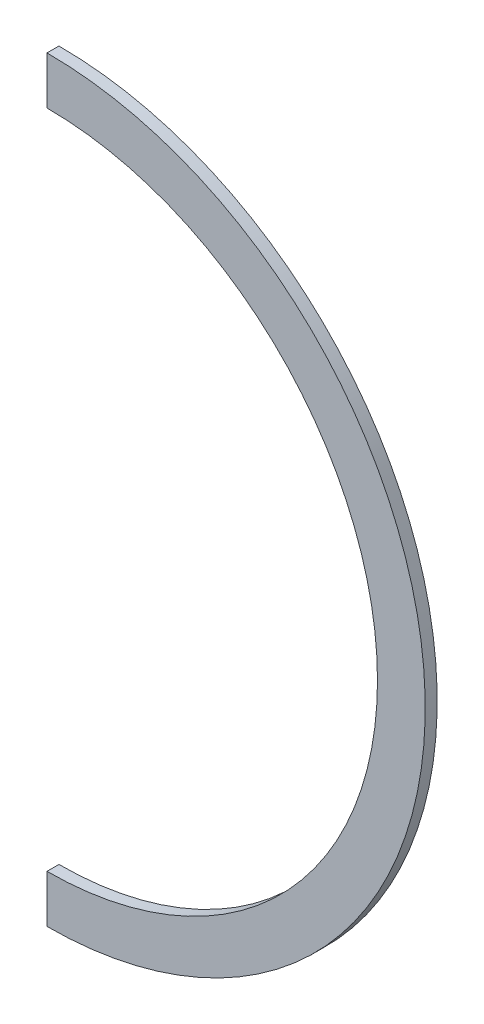
SolidWorks part; units mm, degrees
material "Balsa"
ref_plane "Front Plane" through (0, 0, 0) normal (0, 0, 1) x (1, 0, 0)
ref_plane "Top Plane" through (0, 0, 0) normal (0, 1, 0) x (1, 0, 0)
ref_plane "Right Plane" through (0, 0, 0) normal (1, 0, 0) x (0, 0, -1)
sketch "Sketch2" plane through (0, 0, 0) normal (0, 0, 1) x (1, 0, 0)
  line L0 (0, 0) -> (0, 240.9936) construction
  line L1 (-1.7839, 106.6642) -> (-1.7839, 99.822) construction
  line L2 (1.7839, 106.6642) -> (1.7839, 99.822) construction
  line L3 (-1.7839, 99.822) -> (1.7839, 99.822) construction
  line L4 (-87.7705, -42.8471) -> (-87.8712, -42.9053) construction
  line L5 (-604.1774, -338.907) -> (0, 9.8743) construction
  line L6 (-89.5483, -39.7674) -> (-83.8289, -36.4657) construction
  line L7 (-87.7705, -42.8471) -> (-82.0511, -39.5454) construction
  line L8 (-83.8289, -36.4657) -> (-82.0511, -39.5454) construction
  line L9 (604.1774, -338.907) -> (0, 9.8743) construction
  line L10 (87.7705, -42.8471) -> (82.0511, -39.5454) construction
  line L11 (87.7705, -42.8471) -> (87.8712, -42.9053) construction
  line L12 (89.5483, -39.7674) -> (83.8289, -36.4657) construction
  line L13 (83.8289, -36.4657) -> (82.0511, -39.5454) construction
  arc A0 (-7.652, 93.6463) -> (7.652, 93.6463) centre (0, 6.0782) ccw
  arc A1 (-1.7839, 106.6642) -> (-89.5483, -39.7674) centre (0, 6.0782) ccw
  arc A6 (-1.778, 93.962) -> (-7.652, 93.6463) centre (0, 6.0782) ccw
  circle A7 centre (0, 6.0782) radius 87.9018 construction
  arc A8 (0, 93.98) -> (-1.778, 93.962) centre (0, 6.0782) ccw
  arc A9 (1.778, 93.962) -> (0, 93.98) centre (0, 6.0782) ccw
  arc A10 (1.778, 93.962) -> (0, 93.98) centre (0, 6.0782) ccw construction
  arc A12 (7.652, 93.6463) -> (1.778, 93.962) centre (0, 6.0782) ccw
  arc A13 (0, 93.98) -> (-1.778, 93.962) centre (0, 6.0782) ccw construction
  arc A15 (7.652, 93.6463) -> (1.778, 93.962) centre (0, 6.0782) ccw construction
  arc A16 (-1.778, 93.962) -> (-7.652, 93.6463) centre (0, 6.0782) ccw construction
  arc A17 (0, 106.68) -> (-1.7839, 106.6642) centre (0, 6.0782) ccw
  circle A18 centre (0, 6.0782) radius 100.6018 construction
  arc A19 (1.7839, 106.6642) -> (0, 106.68) centre (0, 6.0782) ccw
  arc A20 (-87.8712, -42.9053) -> (87.8712, -42.9053) centre (0, 6.0782) ccw
  arc A21 (-89.5483, -39.7674) -> (-88.7234, -41.3442) centre (0, 6.0782) ccw
  arc A22 (-88.7234, -41.3442) -> (-87.8712, -42.9053) centre (0, 6.0782) ccw
  arc A23 (87.8712, -42.9053) -> (88.7234, -41.3442) centre (0, 6.0782) ccw
  arc A24 (89.5483, -39.7674) -> (1.7839, 106.6642) centre (0, 6.0782) ccw
  arc A25 (88.7234, -41.3442) -> (89.5483, -39.7674) centre (0, 6.0782) ccw
  point P25 (0, 99.822)
  dimension "D3" = 119.997
  dimension "D8" = 12.7
  dimension "D6" = 87.9018
  dimension "D2" = 1.7839
  dimension "D4" = 9.8743
  dimension "D5" = 3.556
  dimension "D1" = 93.98
  dimension "D7" = 5.842
  dimension "D9" = 6.604
  dimension "D10" = 3.556
extrude "Boss-Extrude1" add sketch "Sketch2" against normal blind 3.175
split "Split1" trim tools "Right Plane" bodies to split 101 resulting bodies 102 103
sketch "Sketch3" plane through (0, 0, 0) normal (1, 0, 0) x (0, 0, -1)
  line L5 (-72.4915, 152.7087) -> (76.812, 152.7087)
  line L6 (-72.4915, 152.7087) -> (-72.4915, -135.9702)
  line L7 (-72.4915, -135.9702) -> (76.812, -135.9702)
  line L8 (76.812, 152.7087) -> (76.812, -135.9702)
extrude "Cut-Extrude1" cut sketch "Sketch3" against normal through all
